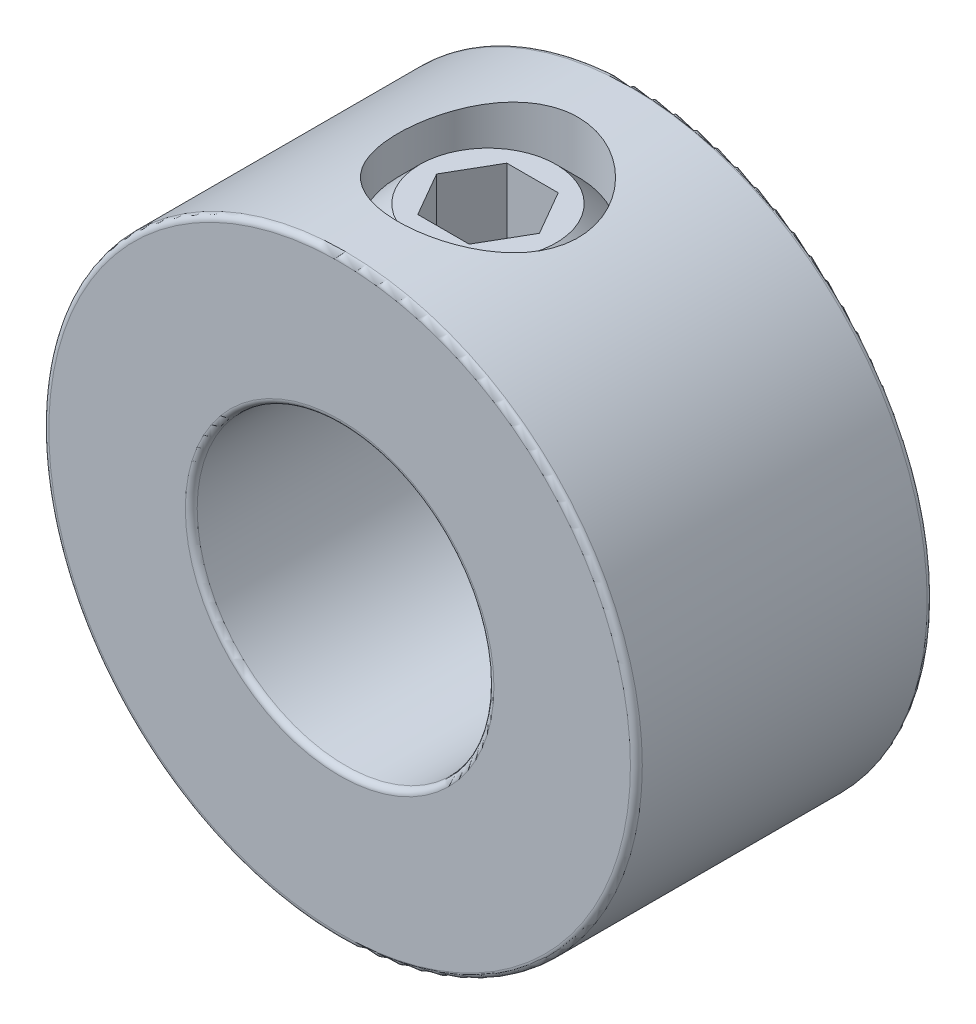
SolidWorks part; units mm, degrees
ref_plane "Front Plane" through (0, 0, 0) normal (0, 0, 1) x (1, 0, 0)
ref_plane "Top Plane" through (0, 0, 0) normal (0, 1, 0) x (1, 0, 0)
ref_plane "Right Plane" through (0, 0, 0) normal (1, 0, 0) x (0, 0, -1)
sketch "Sketch1" plane through (0, 0, 0) normal (0, 0, 1) x (1, 0, 0)
  circle A0 centre (0, 0) radius 7.9375
  circle A1 centre (0, 0) radius 3.9688
  point P4 (7.9375, 0)
  dimension "Bore Dia" = 7.9375
  dimension "OD" = 15.875
extrude "Extrude1" add sketch "Sketch1" along normal mid plane 7.9375
sketch "Sketch2" plane through (41.275, 0, 0) normal (0, -1, 0) x (0, 0, -1)
  line L0 (3.9688, -41.275) -> (-3.9688, -41.275) construction
  line L1 (-3.9688, -33.3375) -> (-3.9688, -49.2125) construction
  line L2 (3.9688, -49.2125) -> (3.9688, -33.3375) construction
  circle A0 centre (0, -41.275) radius 2.413
  point P7 (0, -43.688)
  dimension "Set Screw Dia" = 4.826
extrude "Cut-Extrude1" cut sketch "Sketch2" against normal through all
fillet "Fillet1" radius 0.1588 4 edges at (3.9688, 0, -3.9688) (3.9688, 0, 3.9688) (7.9375, 0, -3.9688) (7.9375, 0, 3.9688)
sketch "Sketch3" plane through (0, 0, 0) normal (0, 0, 1) x (1, 0, 0)
  line L0 (-1.8198, 3.9688) -> (-0.7119, 3.9688)
  line L1 (0, 4.6806) -> (-0.7119, 3.9688)
  line L2 (0, 4.6806) -> (0, 7.1437)
  line L3 (0, 7.1437) -> (-1.8198, 7.1437)
  line L4 (-2.413, 4.562) -> (-2.413, 6.5505)
  line L5 (0, 3.9688) -> (0, 0) construction
  line L6 (-2.413, 4.562) -> (-2.413, 3.9688) construction
  line L7 (-2.413, 3.9688) -> (-1.8198, 3.9688) construction
  line L8 (-2.413, 6.5505) -> (-2.413, 7.1437) construction
  line L9 (-1.8198, 3.9688) -> (-2.413, 4.562)
  line L10 (-2.413, 6.5505) -> (-1.8198, 7.1437)
  line L11 (-2.413, 7.1437) -> (-1.8198, 7.1437) construction
  line L12 (-0.7119, 3.9688) -> (0, 3.9688) construction
  line L13 (0, 3.9688) -> (0, 4.6806) construction
  circle A1 centre (0, 0) radius 3.9688 construction
  dimension "D1" = 0.7119
  dimension "D2" = 0.5932
  dimension "Screw Length" = 3.175
revolve "Revolve1" add sketch "Sketch3" angle 360 about L5
sketch "Sketch4" plane through (3.3734, 7.1437, 0) normal (0, -1, 0) x (0, 0, -1)
  line L1 (0, -1.9986) -> (-1.1906, -2.686)
  line L2 (-1.1906, -2.686) -> (-1.1906, -4.0608)
  line L3 (-1.1906, -4.0608) -> (0, -4.7483)
  line L4 (0, -4.7483) -> (1.1906, -4.0608)
  line L5 (1.1906, -4.0608) -> (1.1906, -2.686)
  line L6 (1.1906, -2.686) -> (0, -1.9986)
  circle A0 centre (0, -3.3734) radius 1.1906 construction
  circle A1 centre (0, -3.3734) radius 1.3748 construction
  dimension "D1" = 2.7496
  dimension "Hex Size" = 2.3813
extrude "Cut-Extrude2" cut sketch "Sketch4" along normal blind 2.3813
equation "\"D1@Fillet1\" = \"OD@Sketch1\"*.01"
equation "\"D1@Cut-Extrude2\" = \"Hex Size@Sketch4\""
equation "\"D2@Sketch3\" =(\"Set Screw Dia@Sketch2\"-\"D1@Sketch4\")/3.5"
equation "\"D1@Sketch3\" = \"D2@Sketch3\"*1.2"
